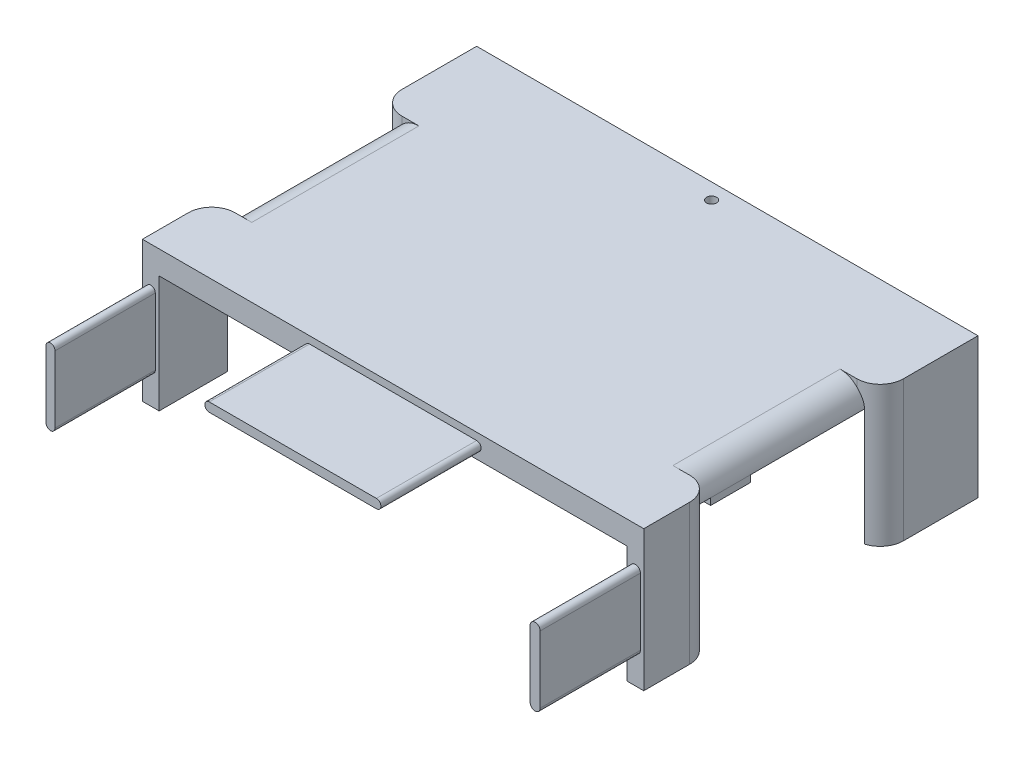
SolidWorks part; units mm, degrees
ref_plane "Front Plane" through (0, 0, 0) normal (0, 0, 1) x (1, 0, 0)
ref_plane "Top Plane" through (0, 0, 0) normal (0, 1, 0) x (1, 0, 0)
ref_plane "Right Plane" through (0, 0, 0) normal (1, 0, 0) x (0, 0, -1)
sketch "Sketch3" plane through (0, 0, 0) normal (0, 0, 1) x (1, 0, 0)
  line L0 (-106.5485, -30.2773) -> (-106.5485, 11.7227)
  line L1 (-106.5485, 11.7227) -> (43.4515, 11.7227)
  line L2 (43.4515, 11.7227) -> (43.4515, -30.2773)
  line L3 (43.4515, -30.2773) -> (38.4515, -30.2773)
  line L4 (38.4515, -30.2773) -> (38.4515, 4.7227)
  line L5 (38.4515, 4.7227) -> (-101.5485, 4.7227)
  line L6 (-101.5485, 4.7227) -> (-101.5485, -30.2773)
  line L7 (-101.5485, -30.2773) -> (-106.5485, -30.2773)
  dimension "D1" = 150
  dimension "D2" = 42
  dimension "D3" = 5
  dimension "D4" = 5
  dimension "D5" = 7
  dimension "D6" = 42
extrude "Boss-Extrude2" add sketch "Sketch3" along normal blind 100
sketch "Sketch4" plane through (0, 0, 100) normal (0, 0, 1) x (1, 0, 0)
  line L0 (-104.0485, -0.2773) -> (-104.0485, -20.2773) construction
  line L1 (-102.6985, -0.2773) -> (-102.6985, -20.2773)
  line L2 (-105.3985, -0.2773) -> (-105.3985, -20.2773)
  line L3 (-56.5485, 8.2227) -> (-6.5485, 8.2227) construction
  line L4 (-56.5485, 9.5727) -> (-6.5485, 9.5727)
  line L5 (-56.5485, 6.8727) -> (-6.5485, 6.8727)
  line L6 (40.9515, -0.2773) -> (40.9515, -20.2773) construction
  line L7 (42.4515, -0.2773) -> (42.4515, -20.2773)
  line L8 (39.4515, -0.2773) -> (39.4515, -20.2773)
  line L11 (-101.5485, 4.7227) -> (38.4515, 4.7227) construction
  line L12 (-106.5485, 11.7227) -> (-106.5485, -30.2773) construction
  line L13 (-101.5485, -30.2773) -> (-101.5485, 4.7227) construction
  line L14 (38.4515, 4.7227) -> (38.4515, -30.2773) construction
  arc A0 (-102.6985, -0.2773) -> (-105.3985, -0.2773) centre (-104.0485, -0.2773) ccw
  arc A1 (-105.3985, -20.2773) -> (-102.6985, -20.2773) centre (-104.0485, -20.2773) ccw
  arc A2 (-56.5485, 9.5727) -> (-56.5485, 6.8727) centre (-56.5485, 8.2227) ccw
  arc A3 (-6.5485, 6.8727) -> (-6.5485, 9.5727) centre (-6.5485, 8.2227) ccw
  arc A4 (42.4515, -0.2773) -> (39.4515, -0.2773) centre (40.9515, -0.2773) ccw
  arc A5 (39.4515, -20.2773) -> (42.4515, -20.2773) centre (40.9515, -20.2773) ccw
  point P2 (-104.0485, -10.2773)
  point P7 (-31.5485, 8.2227)
  point P14 (40.9515, -10.2773)
  dimension "D2" = 2.7
  dimension "D3" = 20
  dimension "D4" = 2.5
  dimension "D5" = 3
  dimension "D6" = 20
  dimension "D7" = 15
  dimension "D8" = 15
  dimension "D9" = 3.5
  dimension "D10" = 2.7
  dimension "D11" = 75
  dimension "D12" = 50
  dimension "D13" = 2.5
extrude "Boss-Extrude3" add sketch "Sketch4" along normal blind 30
sketch "Sketch10" plane through (43.4515, 0, 0) normal (1, 0, 0) x (0, 0, -1)
  line L0 (0, -30.2773) -> (0, 11.7227) construction
  line L1 (-100, 11.7227) -> (0, 11.7227) construction
  circle A0 centre (-45, -8.2773) radius 7.5
  dimension "D1" = 15
  dimension "D2" = 45
  dimension "D3" = 20
extrude "Cut-Extrude2" cut sketch "Sketch10" against normal blind 210
ref_plane "Plane1" through (0, 0, 25) normal (0, 0, -1) x (-1, 0, 0)
ref_plane "Plane2" through (-31.5485, 0, 0) normal (-1, 0, 0) x (0, 0, 1)
sketch "Sketch15" plane through (0, 11.7227, 0) normal (0, 1, 0) x (1, 0, 0)
  line L0 (-31.5485, 23.1) -> (-31.5485, -23.1) construction
  line L1 (43.4515, -100) -> (43.4515, 0) construction
  line L2 (-106.5485, -100) -> (-106.5485, 0) construction
  circle A0 centre (-31.5485, -4.7142) radius 1.5
  dimension "D1" = 3
  dimension "D2" = 75
  dimension "D3" = 75
extrude "Cut-Extrude3" cut sketch "Sketch15" against normal blind 10
sketch "Sketch16" plane through (0, 4.7227, 0) normal (0, -1, 0) x (1, 0, 0)
  line L0 (38.4515, 75) -> (18.4515, 75)
  line L1 (38.4515, 100) -> (38.4515, 0) construction
  line L2 (18.4515, 75) -> (18.4515, 63)
  line L3 (18.4515, 63) -> (38.4515, 63)
  line L4 (38.4515, 100) -> (38.4515, 0) construction
  line L5 (38.4515, 63) -> (38.4515, 75)
  line L6 (-101.5485, 0) -> (38.4515, 0) construction
  dimension "D1" = 20
  dimension "D2" = 12
  dimension "D3" = 63
extrude "Boss-Extrude5" add sketch "Sketch16" along normal blind 2
sketch "Sketch17" plane through (0, 2.7227, 0) normal (0, -1, 0) x (-1, 0, 0)
  line L0 (-21.4515, -63) -> (-21.4515, -75)
  line L1 (-18.4515, -63) -> (-38.4515, -63) construction
  line L2 (-38.4515, -75) -> (-18.4515, -75) construction
  line L3 (-21.4515, -75) -> (-18.4515, -75)
  line L4 (-18.4515, -75) -> (-18.4515, -63)
  line L5 (-18.4515, -63) -> (-21.4515, -63)
  dimension "D1" = 3
extrude "Boss-Extrude6" add sketch "Sketch17" along normal blind 25
sketch "Sketch19" plane through (18.4515, 0, 0) normal (-1, 0, 0) x (0, 0, 1)
  line L0 (75, -22.2773) -> (63, -22.2773) construction
  circle A0 centre (69.4851, 0.2227) radius 3.5
  circle A1 centre (69.4851, -17.7773) radius 3.5
  dimension "D1" = 7
  dimension "D2" = 7
  dimension "D4" = 4.5
  dimension "D3" = 18
extrude "Cut-Extrude4" cut sketch "Sketch19" against normal blind 1
sketch "Sketch20" plane through (19.4515, 0, 0) normal (-1, 0, 0) x (0, 0, 1)
  circle A0 centre (69.4851, 0.2227) radius 1.55
  circle A1 centre (69.4851, -17.7773) radius 1.55
  dimension "D1" = 3.1
  dimension "D2" = 3.1
extrude "Cut-Extrude5" cut sketch "Sketch20" against normal blind 3
mirror "Mirror6" about plane through (-31.5485, 0, 0) normal (-1, 0, 0) of "Cut-Extrude5", "Cut-Extrude4", "Boss-Extrude5", "Boss-Extrude6"
sketch "Sketch21" plane through (0, 4.7227, 0) normal (0, -1, 0) x (1, 0, 0)
  line L0 (-9.0485, 0) -> (-9.0485, 1.5)
  line L1 (-101.5485, 0) -> (38.4515, 0) construction
  line L2 (-9.0485, 1.5) -> (-54.0485, 1.5)
  line L3 (-54.0485, 1.5) -> (-54.0485, 0)
  line L4 (-54.0485, 0) -> (-9.0485, 0)
  dimension "D1" = 1.5
  dimension "D2" = 45
  dimension "D3" = 52.5
  dimension "D4" = 52.5
extrude "Boss-Extrude7" add sketch "Sketch21" along normal blind 35
sketch "Sketch23" plane through (0, 0, 0) normal (0, 0, -1) x (-1, 0, 0)
  line L1 (9.0485, -30.2773) -> (9.0485, 4.7227) construction
  line L2 (54.0485, -30.2773) -> (54.0485, 4.7227) construction
  line L3 (54.0485, -30.2773) -> (9.0485, -30.2773) construction
  circle A0 centre (44.5485, -16.2773) radius 8.25
  circle A1 centre (18.5485, -16.2773) radius 8.25
  dimension "D1" = 16.5
  dimension "D2" = 16.5
  dimension "D3" = 26
  dimension "D4" = 9.5
  dimension "D5" = 9.5
  dimension "D6" = 14
  dimension "D7" = 14
extrude "Cut-Extrude6" cut sketch "Sketch23" against normal blind 40
sketch "Sketch24" plane through (0, 0, 0) normal (0, 0, -1) x (-1, 0, 0)
  line L0 (26.5485, -26.3207) -> (36.5485, -26.3207) construction
  line L1 (26.5485, -23.0953) -> (36.5485, -23.0953)
  line L2 (26.5485, -29.5461) -> (36.5485, -29.5461)
  line L3 (9.0485, -30.2773) -> (9.0485, 4.7227) construction
  line L4 (54.0485, -30.2773) -> (54.0485, 4.7227) construction
  arc A0 (26.5485, -23.0953) -> (26.5485, -29.5461) centre (26.5485, -26.3207) ccw
  arc A1 (36.5485, -29.5461) -> (36.5485, -23.0953) centre (36.5485, -26.3207) ccw
  point P2 (31.5485, -26.3207)
  dimension "D1" = 10
  dimension "D2" = 22.5
  dimension "D3" = 22.5
extrude "Cut-Extrude7" cut sketch "Sketch24" against normal blind 40
sketch "Sketch26" plane through (-106.5485, 0, 0) normal (-1, 0, 0) x (0, 0, 1)
  line L0 (29.2717, -30.2773) -> (29.2717, 11.7227)
  line L1 (100, -30.2773) -> (0, -30.2773) construction
  line L2 (100, 11.7227) -> (0, 11.7227) construction
  line L3 (29.2717, 11.7227) -> (79.2717, 11.7227)
  line L4 (79.2717, 11.7227) -> (79.2717, -30.2773)
  line L5 (79.2717, -30.2773) -> (29.2717, -30.2773)
  line L6 (0, 11.7227) -> (0, -30.2773) construction
  dimension "D1" = 50
  dimension "D2" = 29.2717
extrude "Cut-Extrude8" cut sketch "Sketch26" against normal blind 5
fillet "Fillet1" radius 7 1 edges at (-101.5485, 11.7227, 54.2717)
fillet "Fillet3" radius 7 1 edges at (-106.5485, -9.2773, 29.2717)
fillet "Fillet4" radius 7 1 edges at (-106.5485, -9.2773, 79.2717)
sketch "Sketch27" plane through (43.4515, 0, 0) normal (1, 0, 0) x (0, 0, -1)
  line L0 (-29.27, -30.2773) -> (-29.27, 11.7227)
  line L1 (-100, -30.2773) -> (0, -30.2773) construction
  line L2 (-100, 11.7227) -> (0, 11.7227) construction
  line L3 (-29.27, 11.7227) -> (-79.2717, 11.7227)
  line L4 (-79.2717, 11.7227) -> (-79.2717, -30.2773)
  line L5 (-79.2717, -30.2773) -> (-29.27, -30.2773)
  line L6 (0, -30.2773) -> (0, 11.7227) construction
  dimension "D1" = 29.27
  dimension "D2" = 50.0017
extrude "Cut-Extrude9" cut sketch "Sketch27" against normal blind 5
fillet "Fillet5" radius 7 1 edges at (38.4515, 11.7227, 54.2708)
fillet "Fillet6" radius 7 1 edges at (43.4515, -9.2773, 29.27)
fillet "Fillet7" radius 7 1 edges at (43.4515, -9.2773, 79.2717)
